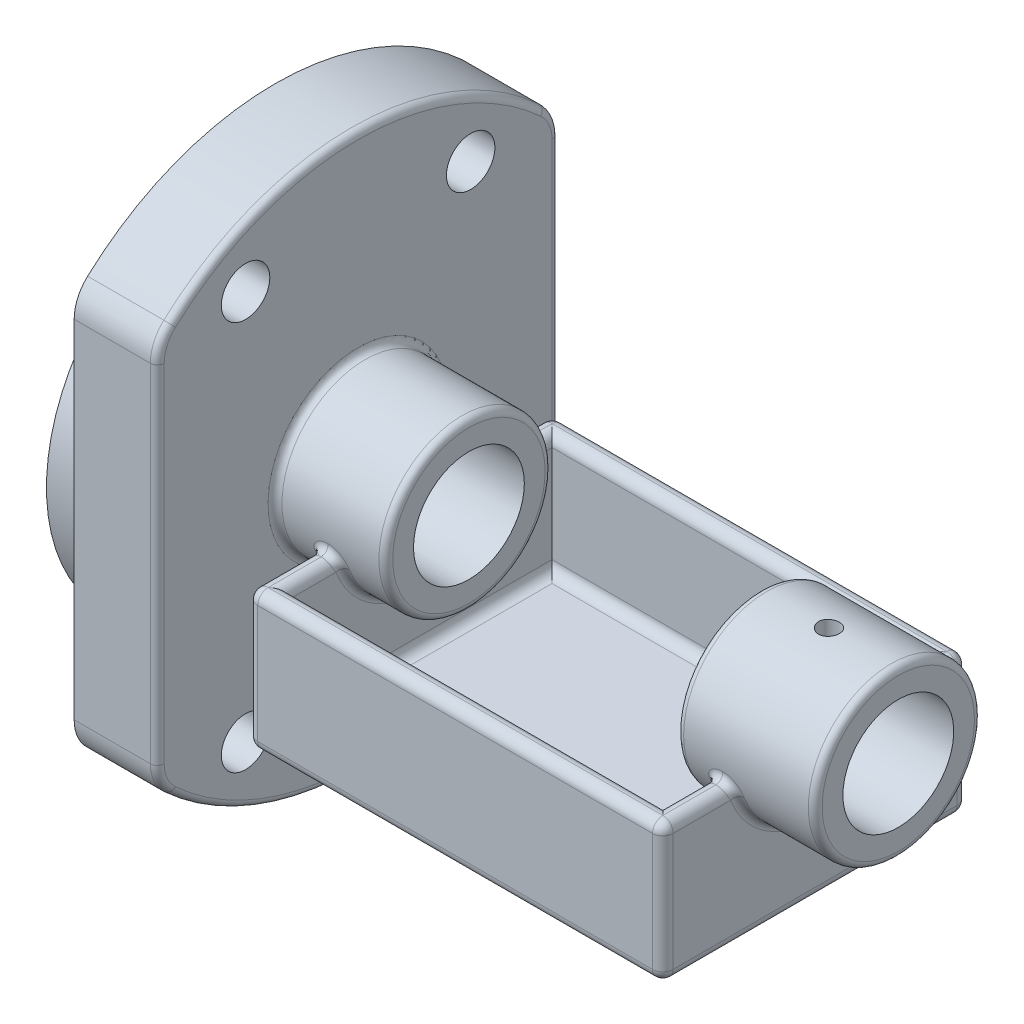
SolidWorks part; units mm, degrees
ref_plane "前基準面" through (0, 0, 0) normal (0, 0, 1) x (1, 0, 0)
ref_plane "上基準面" through (0, 0, 0) normal (0, 1, 0) x (1, 0, 0)
ref_plane "右基準面" through (0, 0, 0) normal (1, 0, 0) x (0, 0, -1)
sketch "草圖1" plane through (0, 0, 0) normal (0, 0, 1) x (1, 0, 0)
  line L1 (-12, -3) -> (-72, -3)
  line L2 (-12, -3) -> (-12, -23)
  line L3 (-12, -23) -> (-72, -23)
  line L4 (-72, -3) -> (-72, -23)
  dimension "D1" = 3
  dimension "D2" = 12
  dimension "D3" = 20
  dimension "D4" = 60
extrude "填料-伸長1" add sketch "草圖1" along normal mid plane 44
shell "薄殼1" thickness 3 removed face at (-42, -3, 0)
fillet "圓角1" radius 1.5 16 edges at (-72, -23, 0) (-42, -23, 22) (-12, -23, 0) (-42, -23, -22) (-69, -3, 0) (-42, -3, 19) (-15, -3, 0) (-42, -3, -19) (-12, -3, 0) (-42, -3, 22) (-72, -3, 0) (-42, -3, -22) (-72, -13, -22) (-72, -13, 22) (-12, -13, -22) (-12, -13, 22)
fillet "圓角2" radius 1.5 4 edges at (-15, -20, 0) (-42, -20, 19) (-69, -20, 0) (-42, -20, -19)
sketch "草圖2" plane through (0, 0, 0) normal (0, 0, 1) x (1, 0, 0)
  line L0 (0, 0) -> (-83.4824, 0) construction
  line L1 (0, 0) -> (-20, 0)
  line L2 (0, 0) -> (0, 12)
  line L3 (0, 12) -> (-20, 12)
  line L4 (-20, 0) -> (-20, 12)
  line L5 (-62, 0) -> (-62, 12)
  line L6 (-62, 12) -> (-78, 12)
  line L7 (-78, 12) -> (-78, 40)
  line L8 (-78, 40) -> (-90, 40)
  line L9 (-90, 40) -> (-90, 27)
  line L10 (-90, 27) -> (-96, 27)
  line L11 (-96, 27) -> (-96, 0)
  line L12 (-96, 0) -> (-62, 0)
  dimension "D1" = 6
  dimension "D2" = 28
  dimension "D3" = 12
  dimension "D4" = 54
  dimension "D5" = 80
  dimension "D6" = 20
  dimension "D7" = 24
  dimension "D8" = 96
revolve "旋轉1" add sketch "草圖2" angle 360 about L0
sketch "草圖3" plane through (0, 0, 0) normal (0, 0, 1) x (1, 0, 0)
  line L0 (-96, 27) -> (-96, -27) construction
  line L1 (0, 0) -> (-96, 0)
  line L2 (0, 0) -> (0, 8)
  line L3 (0, 8) -> (-96, 8)
  line L4 (-96, 0) -> (-96, 8)
  line L5 (0, 0) -> (18.9389, 0) construction
  line L6 (-96, 24) -> (-87, 24)
  line L7 (-96, 24) -> (-96, 12)
  line L8 (-96, 12) -> (-87, 12)
  line L9 (-87, 24) -> (-87, 12)
  dimension "D1" = 9
  dimension "D2" = 16
  dimension "D3" = 24
  dimension "D4" = 48
revolve "除料-旋轉1" cut sketch "草圖3" angle 360 about L5
sketch "草圖4" plane through (0, 0, 0) normal (0, 1, 0) x (1, 0, 0)
  circle A0 centre (-10, 0) radius 1.5
  dimension "D2" = 3
  dimension "D1" = 10
extrude "除料-伸長1" cut sketch "草圖4" along normal through all
sketch "草圖5" plane through (0, 0, 0) normal (1, 0, 0) x (0, 0, -1)
  line L0 (0, 0) -> (45.2763, 0) construction
  line L1 (29, 36.2791) -> (55.5079, 36.2791)
  line L2 (29, 36.2791) -> (29, -33.5702)
  line L3 (29, -33.5702) -> (55.5079, -33.5702)
  line L4 (55.5079, 36.2791) -> (55.5079, -33.5702)
  line L5 (0, 0) -> (0, 50.0167) construction
  line L6 (-29, 36.2791) -> (-55.5079, 36.2791)
  line L7 (-29, -33.5702) -> (-55.5079, -33.5702)
  line L8 (-29, 36.2791) -> (-29, -33.5702)
  line L9 (-55.5079, 36.2791) -> (-55.5079, -33.5702)
  circle A0 centre (0, 0) radius 32.5 construction
  circle A1 centre (16.25, 28.1458) radius 3.5
  circle A2 centre (-16.25, 28.1458) radius 3.5
  circle A3 centre (16.25, -28.1458) radius 3.5
  circle A4 centre (-16.25, -28.1458) radius 3.5
  dimension "D1" = 7
  dimension "D2" = 65
  dimension "D3" = 60
  dimension "D4" = 58
extrude "除料-伸長2" cut sketch "草圖5" against normal through all
sketch "草圖6" plane through (0, 0, 0) normal (0, 0, 1) x (1, 0, 0)
  line L0 (-78, -38) -> (-13.1611, -22.9612)
  line L1 (-78, -40) -> (-78, -27.55) construction
  line L2 (-90, -40) -> (-78, -40) construction
  arc A0 (-13.5, -23) -> (-12, -21.5) centre (-13.5, -21.5) ccw construction
  dimension "D1" = 2
rib "肋材1" sketch "草圖6" sketch "草圖6" thickness 6 extrusion direction parallel to sketch draft on no parameters "D1"=6
chamfer "導角1" distance 1 angle 45 2 edges at (-20, 0, 8) (-96, 0, 8)
fillet "圓角4" radius 6 4 edges at (-84, 27.55, 29) (-84, 27.55, -29) (-84, -27.55, -29) (-84, -27.55, 29)
fillet "圓角5" radius 1 25 edges at (-15, -12, 0) (-14.5729, -3.4517, -11.4929) (-12.2834, -3.6225, -11.4402) (-12, -12, 0) (-72, -9.0253, 7.9085) (-71.641, -3.5262, 11.4702) (-72, -9.0253, -7.9085) (-69.4466, -5.5679, -10.6301) (-69.359, -3.5262, -11.4702) (-69, -12, 0) (-78, 27.4532, -28.4933) (-78, 0, -29) (-78, -27.4532, -28.4933) (-78, -40, 0) (-78, -27.4532, 28.4933) (-78, 0, 29) (-78, 27.4532, 28.4933) (0, 0, -12) (-20, 0, -12) (-14.7166, -3.6225, 11.4402) (-12.4271, -3.4517, 11.4929) (-71.5534, -5.5679, 10.6301) (-62, 0, -12) (-78, 12, 0) (-78, 40, 0)
